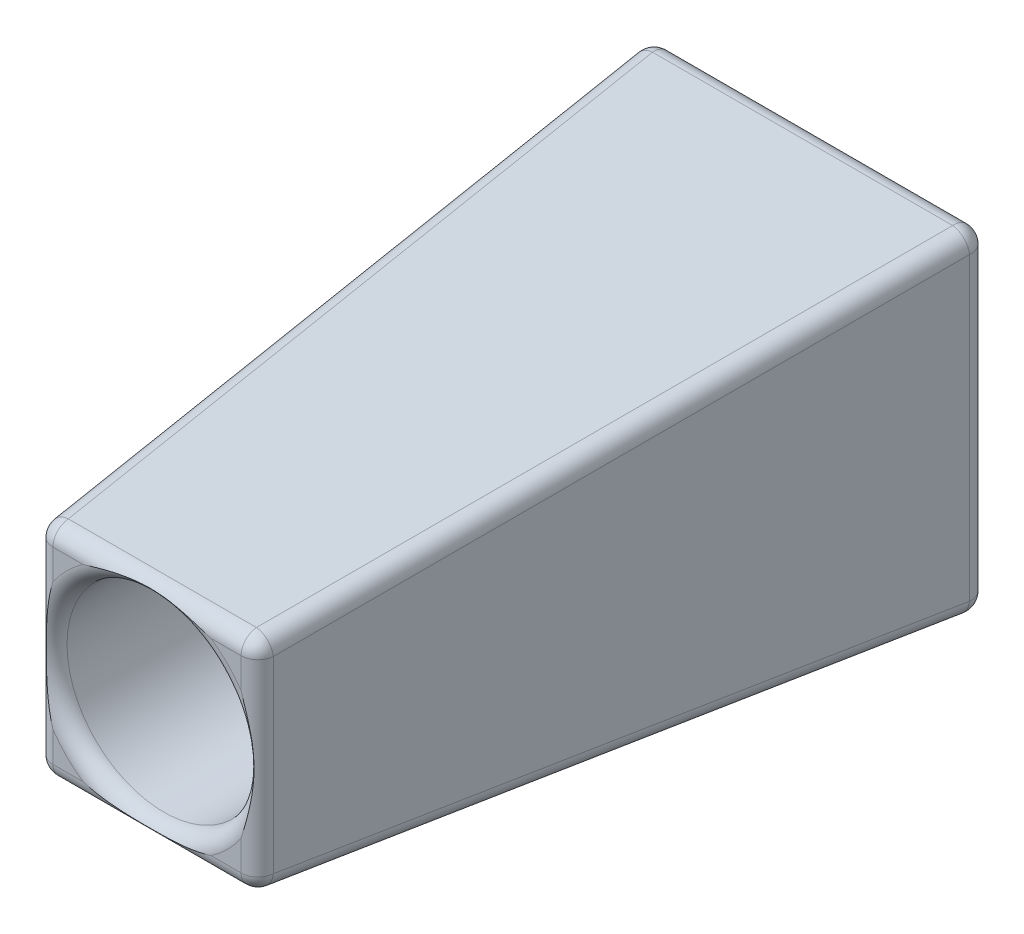
SolidWorks part; units mm, degrees
ref_plane "Front Plane" through (0, 0, 0) normal (0, 0, 1) x (1, 0, 0)
ref_plane "Top Plane" through (0, 0, 0) normal (0, 1, 0) x (1, 0, 0)
ref_plane "Right Plane" through (0, 0, 0) normal (1, 0, 0) x (0, 0, -1)
sketch "Sketch1" plane through (0, 0, 0) normal (0, 0, 1) x (1, 0, 0)
  line L1 (-5, 5) -> (5, 5)
  line L2 (-5, 5) -> (-5, -5)
  line L3 (-5, -5) -> (5, -5)
  line L4 (5, 5) -> (5, -5)
  dimension "D1" = 10
  dimension "D2" = 10
  dimension "D3" = 5
  dimension "D4" = 5
extrude "Boss-Extrude1" add sketch "Sketch1" along normal blind 20
sketch "Sketch2" plane through (5, 0, 0) normal (1, 0, 0) x (0, 0, -1)
  line L0 (0, 5) -> (-20, 3.25)
  line L1 (-20, -5) -> (-20, 5) construction
  line L2 (-20, 3.25) -> (-20, 5)
  line L3 (-20, 5) -> (0, 5)
  line L4 (-22.6291, 0) -> (2.8319, 0) construction
  line L5 (-20, -5) -> (0, -5)
  line L6 (-20, -3.25) -> (-20, -5)
  line L7 (0, -5) -> (-20, -3.25)
  dimension "D1" = 1.75
  dimension "D2" = 0
extrude "Cut-Extrude1" cut sketch "Sketch2" against normal up to surface (10 mm away) up to face at (-5, 0, 10)
ref_plane "Plane1" through (0, 5, 0) normal (0, 1, 0) x (1, 0, 0)
sketch "Sketch5" plane through (0, 5, 0) normal (0, 1, 0) x (1, 0, 0)
  line L0 (-5, 0) -> (-3.25, -20)
  line L1 (-5, -20) -> (5, -20) construction
  line L2 (-3.25, -20) -> (-5, -20)
  line L3 (-5, -20) -> (-5, 0)
  line L4 (0, 0) -> (0, -20.2574) construction
  line L5 (5, 0) -> (-5, 0) construction
  line L6 (5, -20) -> (5, 0)
  line L7 (3.25, -20) -> (5, -20)
  line L8 (5, 0) -> (3.25, -20)
  point P13 (-5, -20)
  dimension "D1" = 1.75
extrude "Cut-Extrude2" cut sketch "Sketch5" against normal up to surface (8.25 mm away) up to face at (0, -4.125, 10)
sketch "Sketch6" plane through (0, 0, 20) normal (0, 0, 1) x (1, 0, 0)
  circle A0 centre (0, 0) radius 2.875
  dimension "D1" = 5.75
extrude "Cut-Extrude3" cut sketch "Sketch6" against normal blind 15
fillet "Fillet1" radius 0.5 13 edges at (5, 0, 0) (3.25, 0, 20) (4.125, -4.125, 10) (0, -5, 0) (0, -3.25, 20) (-3.25, 0, 20) (-4.125, -4.125, 10) (-5, 0, 0) (4.125, 4.125, 10) (0, 3.25, 20) (-4.125, 4.125, 10) (0, 5, 0) (2.875, 0, 20)
